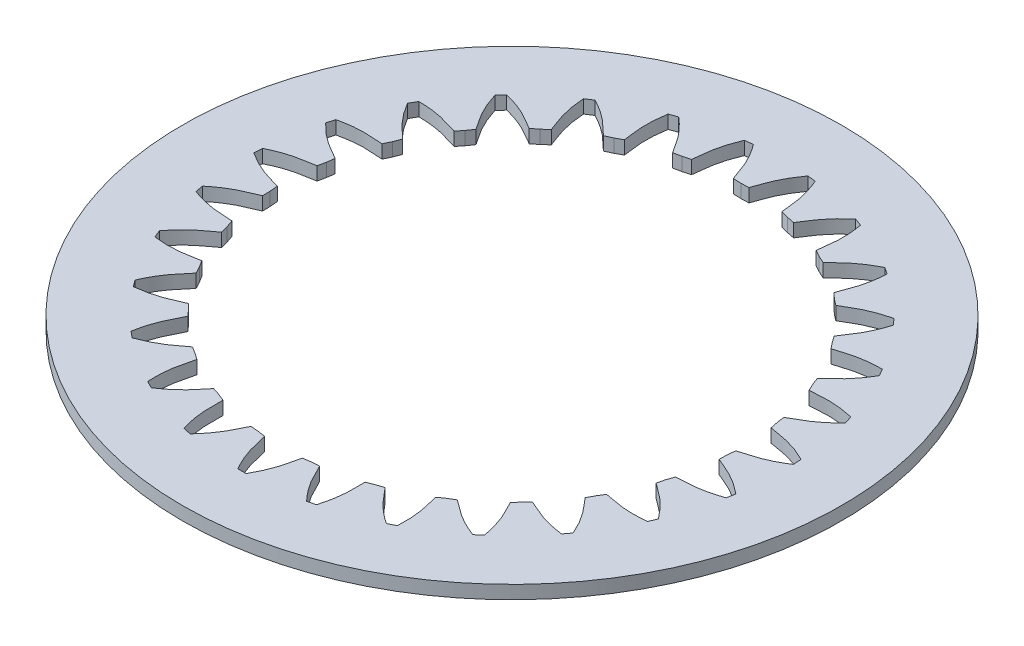
SolidWorks part; units mm, degrees
ref_plane "Plano frontal" through (0, 0, 0) normal (0, 0, 1) x (1, 0, 0)
ref_plane "Plano superior" through (0, 0, 0) normal (0, 1, 0) x (1, 0, 0)
ref_plane "Plano direito" through (0, 0, 0) normal (1, 0, 0) x (0, 0, -1)
sketch "Esboço1" plane through (0, 0, 0) normal (0, 1, 0) x (1, 0, 0)
  line L0 (-63.1274, 27.2305) -> (-64.1343, 25.1074)
  line L1 (-67.3802, 14.2655) -> (-67.7055, 11.9383)
  line L2 (-67.7055, 11.9383) -> (-68.1957, 9.6402)
  line L3 (-80.9062, 5.9542) -> (-81.0504, 3.4787)
  line L4 (-62.2741, 29.4199) -> (-63.1274, 27.2305)
  line L5 (-77.3522, 24.4519) -> (-78.0634, 22.0765)
  line L6 (-55.146, 41.0547) -> (-56.6154, 39.221)
  line L7 (-53.8108, 42.9883) -> (-55.146, 41.0547)
  line L8 (-69.6282, 41.6315) -> (-70.868, 39.4841)
  line L9 (-44.1916, 52.6656) -> (-46.0444, 51.2202)
  line L10 (-42.4465, 54.2391) -> (-44.1916, 52.6656)
  line L11 (-58.1505, 56.5667) -> (-59.8521, 54.763)
  line L12 (-30.8549, 61.4372) -> (-32.991, 60.4581)
  line L13 (-28.794, 62.566) -> (-30.8549, 61.4372)
  line L14 (-43.5379, 68.4523) -> (-45.6096, 67.0897)
  line L15 (-15.8548, 66.8968) -> (-18.1592, 66.4367)
  line L16 (-13.5891, 67.5198) -> (-15.8548, 66.8968)
  line L17 (-26.5781, 76.6477) -> (-28.9082, 75.7996)
  line L18 (0, 68.75) -> (-2.3483, 68.8337)
  line L19 (2.3483, 68.8337) -> (0, 68.75)
  line L20 (-8.1855, 80.711) -> (-10.6484, 80.4231)
  line L21 (15.8548, 66.8968) -> (13.5891, 67.5198)
  line L22 (18.1592, 66.4367) -> (15.8548, 66.8968)
  line L23 (10.6484, 80.4231) -> (8.1855, 80.711)
  line L24 (30.8549, 61.4372) -> (28.794, 62.566)
  line L25 (32.991, 60.4581) -> (30.8549, 61.4372)
  line L26 (28.9082, 75.7996) -> (26.5781, 76.6477)
  line L27 (44.1916, 52.6656) -> (42.4465, 54.2391)
  line L28 (46.0444, 51.2202) -> (44.1916, 52.6656)
  line L29 (45.6096, 67.0897) -> (43.5379, 68.4523)
  line L30 (55.146, 41.0547) -> (53.8108, 42.9883)
  line L31 (56.6154, 39.221) -> (55.146, 41.0547)
  line L32 (59.8521, 54.763) -> (58.1505, 56.5667)
  line L33 (63.1274, 27.2305) -> (62.2741, 29.4199)
  line L34 (64.1343, 25.1074) -> (63.1274, 27.2305)
  line L35 (70.868, 39.4841) -> (69.6282, 41.6315)
  line L36 (67.7055, 11.9383) -> (67.3802, 14.2655)
  line L37 (68.1957, 9.6402) -> (67.7055, 11.9383)
  line L38 (78.0634, 22.0765) -> (77.3522, 24.4519)
  line L39 (68.6337, -3.9975) -> (68.8538, -1.658)
  line L40 (68.5807, -6.3467) -> (68.6337, -3.9975)
  line L41 (81.0504, 3.4787) -> (80.9062, 5.9542)
  line L42 (65.8618, -19.7177) -> (66.6155, -17.4921)
  line L43 (65.2685, -21.9914) -> (65.8618, -19.7177)
  line L44 (79.6679, -15.3065) -> (80.0985, -12.8646)
  line L45 (59.5392, -34.375) -> (60.7859, -32.3831)
  line L46 (58.4376, -36.4506) -> (59.5392, -34.375)
  line L47 (73.9905, -33.2666) -> (74.9726, -30.9898)
  line L48 (50.0069, -47.1791) -> (51.6793, -45.5284)
  line L49 (48.4563, -48.9447) -> (50.0069, -47.1791)
  line L50 (64.3243, -49.4333) -> (65.805, -47.4444)
  line L51 (37.7787, -57.4398) -> (39.7867, -56.2193)
  line L52 (35.8627, -58.8001) -> (37.7787, -57.4398)
  line L53 (51.1903, -62.935) -> (53.0898, -61.3412)
  line L54 (23.5139, -64.6039) -> (25.7492, -63.8794)
  line L55 (21.3358, -65.4857) -> (23.5139, -64.6039)
  line L56 (35.2966, -73.0439) -> (37.5125, -71.9311)
  line L57 (7.9814, -68.2851) -> (10.3235, -68.0957)
  line L58 (5.6587, -68.6409) -> (7.9814, -68.2851)
  line L59 (17.5001, -79.215) -> (19.9129, -78.6431)
  line L60 (-7.9814, -68.2851) -> (-5.6587, -68.6409)
  line L61 (-10.3235, -68.0957) -> (-7.9814, -68.2851)
  line L62 (-1.2398, -81.1155) -> (1.2398, -81.1155)
  line L63 (-23.5139, -64.6039) -> (-21.3358, -65.4857)
  line L64 (-25.7492, -63.8794) -> (-23.5139, -64.6039)
  line L65 (-19.9129, -78.6431) -> (-17.5001, -79.215)
  line L66 (-37.7787, -57.4398) -> (-35.8627, -58.8001)
  line L67 (-39.7867, -56.2193) -> (-37.7787, -57.4398)
  line L68 (-37.5125, -71.9311) -> (-35.2966, -73.0439)
  line L69 (-50.0069, -47.1791) -> (-48.4563, -48.9447)
  line L70 (-51.6793, -45.5284) -> (-50.0069, -47.1791)
  line L71 (-53.0898, -61.3412) -> (-51.1903, -62.935)
  line L72 (-59.5392, -34.375) -> (-58.4376, -36.4506)
  line L73 (-60.7859, -32.3831) -> (-59.5392, -34.375)
  line L74 (-65.805, -47.4444) -> (-64.3243, -49.4333)
  line L75 (-65.8618, -19.7177) -> (-65.2685, -21.9914)
  line L76 (-66.6155, -17.4921) -> (-65.8618, -19.7177)
  line L77 (-74.9726, -30.9898) -> (-73.9905, -33.2666)
  line L78 (-68.6337, -3.9975) -> (-68.5807, -6.3467)
  line L79 (-68.8538, -1.658) -> (-68.6337, -3.9975)
  line L80 (-80.0985, -12.8646) -> (-79.6679, -15.3065)
  circle A0 centre (0, 0) radius 99
  spline S0 degree 3 number of poles 788 (-68.1957, 9.6402) -> (-80.9062, 5.9542)
  spline S1 degree 3 number of poles 788 (-78.0634, 22.0765) -> (-67.3802, 14.2655)
  spline S2 degree 3 number of poles 788 (-70.868, 39.4841) -> (-62.2741, 29.4199)
  spline S3 degree 3 number of poles 788 (-64.1343, 25.1074) -> (-77.3522, 24.4519)
  spline S4 degree 3 number of poles 788 (-59.8521, 54.763) -> (-53.8108, 42.9883)
  spline S5 degree 3 number of poles 788 (-56.6154, 39.221) -> (-69.6282, 41.6315)
  spline S6 degree 3 number of poles 788 (-45.6096, 67.0897) -> (-42.4465, 54.2391)
  spline S7 degree 3 number of poles 788 (-46.0444, 51.2202) -> (-58.1505, 56.5667)
  spline S8 degree 3 number of poles 788 (-28.9082, 75.7996) -> (-28.794, 62.566)
  spline S9 degree 3 number of poles 788 (-32.991, 60.4581) -> (-43.5379, 68.4523)
  spline S10 degree 3 number of poles 788 (-10.6484, 80.4231) -> (-13.5891, 67.5198)
  spline S11 degree 3 number of poles 788 (-18.1592, 66.4367) -> (-26.5781, 76.6477)
  spline S12 degree 3 number of poles 788 (8.1855, 80.711) -> (2.3483, 68.8337)
  spline S13 degree 3 number of poles 788 (-2.3483, 68.8337) -> (-8.1855, 80.711)
  spline S14 degree 3 number of poles 788 (26.5781, 76.6477) -> (18.1592, 66.4367)
  spline S15 degree 3 number of poles 788 (13.5891, 67.5198) -> (10.6484, 80.4231)
  spline S16 degree 3 number of poles 788 (43.5379, 68.4523) -> (32.991, 60.4581)
  spline S17 degree 3 number of poles 788 (28.794, 62.566) -> (28.9082, 75.7996)
  spline S18 degree 3 number of poles 788 (58.1505, 56.5667) -> (46.0444, 51.2202)
  spline S19 degree 3 number of poles 788 (42.4465, 54.2391) -> (45.6096, 67.0897)
  spline S20 degree 3 number of poles 788 (69.6282, 41.6315) -> (56.6154, 39.221)
  spline S21 degree 3 number of poles 788 (53.8108, 42.9883) -> (59.8521, 54.763)
  spline S22 degree 3 number of poles 788 (77.3522, 24.4519) -> (64.1343, 25.1074)
  spline S23 degree 3 number of poles 788 (62.2741, 29.4199) -> (70.868, 39.4841)
  spline S24 degree 3 number of poles 788 (80.9062, 5.9542) -> (68.1957, 9.6402)
  spline S25 degree 3 number of poles 788 (67.3802, 14.2655) -> (78.0634, 22.0765)
  spline S26 degree 3 number of poles 788 (80.0985, -12.8646) -> (68.5807, -6.3467)
  spline S27 degree 3 number of poles 788 (68.8538, -1.658) -> (81.0504, 3.4787)
  spline S28 degree 3 number of poles 788 (74.9726, -30.9898) -> (65.2685, -21.9914)
  spline S29 degree 3 number of poles 788 (66.6155, -17.4921) -> (79.6679, -15.3065)
  spline S30 degree 3 number of poles 788 (65.805, -47.4444) -> (58.4376, -36.4506)
  spline S31 degree 3 number of poles 788 (60.7859, -32.3831) -> (73.9905, -33.2666)
  spline S32 degree 3 number of poles 788 (53.0898, -61.3412) -> (48.4563, -48.9447)
  spline S33 degree 3 number of poles 788 (51.6793, -45.5284) -> (64.3243, -49.4333)
  spline S34 degree 3 number of poles 788 (37.5125, -71.9311) -> (35.8627, -58.8001)
  spline S35 degree 3 number of poles 788 (39.7867, -56.2193) -> (51.1903, -62.935)
  spline S36 degree 3 number of poles 788 (19.9129, -78.6431) -> (21.3358, -65.4857)
  spline S37 degree 3 number of poles 788 (25.7492, -63.8794) -> (35.2966, -73.0439)
  spline S38 degree 3 number of poles 788 (1.2398, -81.1155) -> (5.6587, -68.6409)
  spline S39 degree 3 number of poles 788 (10.3235, -68.0957) -> (17.5001, -79.215)
  spline S40 degree 3 number of poles 788 (-17.5001, -79.215) -> (-10.3235, -68.0957)
  spline S41 degree 3 number of poles 788 (-5.6587, -68.6409) -> (-1.2398, -81.1155)
  spline S42 degree 3 number of poles 788 (-35.2966, -73.0439) -> (-25.7492, -63.8794)
  spline S43 degree 3 number of poles 788 (-21.3358, -65.4857) -> (-19.9129, -78.6431)
  spline S44 degree 3 number of poles 788 (-51.1903, -62.935) -> (-39.7867, -56.2193)
  spline S45 degree 3 number of poles 788 (-35.8627, -58.8001) -> (-37.5125, -71.9311)
  spline S46 degree 3 number of poles 788 (-64.3243, -49.4333) -> (-51.6793, -45.5284)
  spline S47 degree 3 number of poles 788 (-48.4563, -48.9447) -> (-53.0898, -61.3412)
  spline S48 degree 3 number of poles 788 (-73.9905, -33.2666) -> (-60.7859, -32.3831)
  spline S49 degree 3 number of poles 788 (-58.4376, -36.4506) -> (-65.805, -47.4444)
  spline S50 degree 3 number of poles 788 (-79.6679, -15.3065) -> (-66.6155, -17.4921)
  spline S51 degree 3 number of poles 788 (-65.2685, -21.9914) -> (-74.9726, -30.9898)
  spline S52 degree 3 number of poles 788 (-81.0504, 3.4787) -> (-68.8538, -1.658)
  spline S53 degree 3 number of poles 788 (-68.5807, -6.3467) -> (-80.0985, -12.8646)
  point P165 (0, 0)
  dimension "D1" = 27
extrude "Ressalto-extrusão2" add sketch "Esboço1" along normal blind 4
